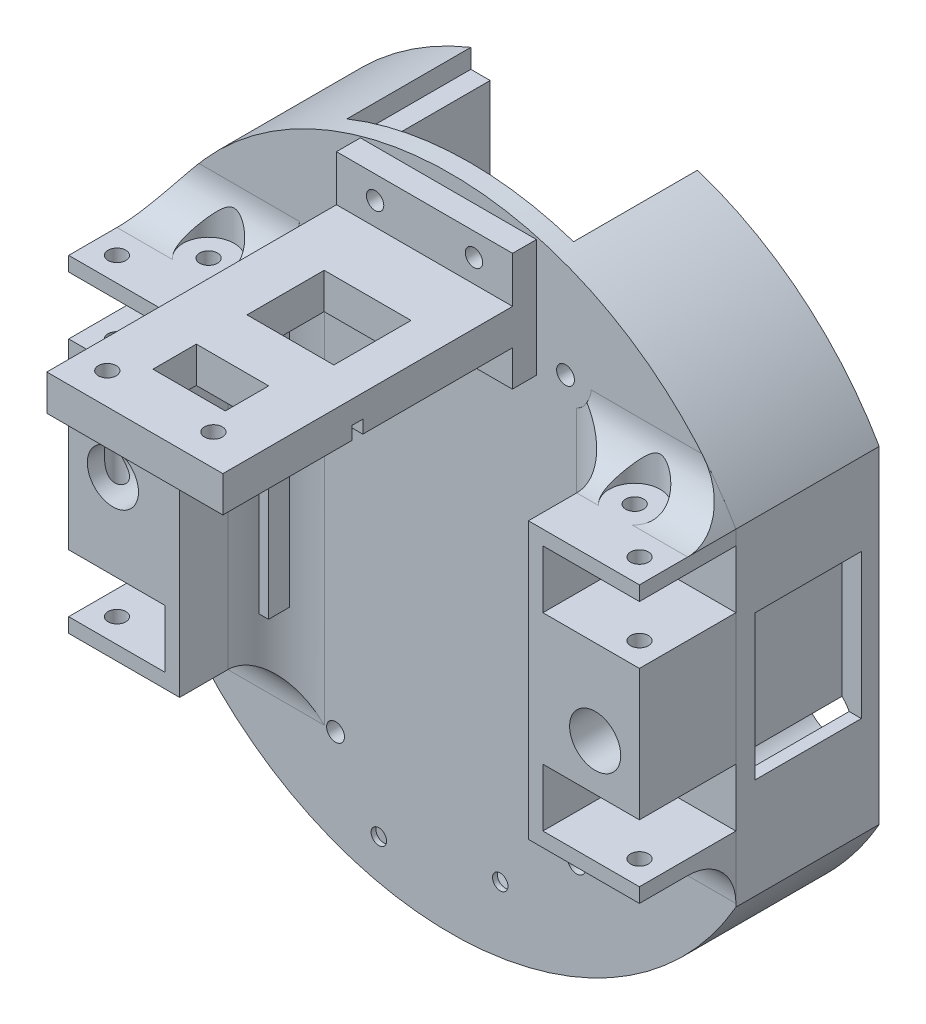
SolidWorks part; units mm, degrees
ref_plane "Alzado" through (0, 0, 0) normal (0, 0, 1) x (1, 0, 0)
ref_plane "Planta" through (0, 0, 0) normal (0, 1, 0) x (1, 0, 0)
ref_plane "Vista lateral" through (0, 0, 0) normal (1, 0, 0) x (0, 0, -1)
sketch "Croquis1" plane through (0, 0, 0) normal (0, 0, 1) x (1, 0, 0)
  line L0 (-13.4238, -120.2944) -> (-13.4238, -132.2944) construction
  line L1 (-13.4238, -132.2944) -> (-9.4238, -132.2944) construction
  line L2 (-9.4238, -132.2944) -> (-9.4238, -256.2944) construction
  line L3 (-9.4238, -256.2944) -> (33.5762, -256.2944) construction
  line L4 (33.5762, -120.2944) -> (33.5762, -256.2944) construction
  line L5 (-13.4238, -120.2944) -> (-13.4238, -132.2944)
  line L6 (-13.4238, -132.2944) -> (-9.4238, -132.2944)
  line L7 (-9.4238, -132.2944) -> (-9.4238, -256.2944)
  line L8 (-9.4238, -256.2944) -> (33.5762, -256.2944)
  line L9 (33.5762, -120.2944) -> (33.5762, -256.2944)
  circle A2 centre (12.066, -191.5898) radius 68.188
  circle A3 centre (12.066, -191.5898) radius 43.8976
extrude "Saliente-Extruir2" add sketch "Croquis1" along normal blind 25.7 contours A3 L7 L6 L5 A2 L9 L8 region at (-15.328, -130.3199, 0)
sketch "Croquis3" plane through (0, 0, 25.7) normal (0, 0, 1) x (1, 0, 0)
  circle A0 centre (12.066, -191.5898) radius 68.188
extrude "Saliente-Extruir3" add sketch "Croquis3" along normal blind 4
sketch "Croquis6" plane through (0, 0, 29.7) normal (0, 0, 1) x (1, 0, 0)
  line L0 (-47.0808, -157.6597) -> (-47.0808, -225.5199)
  line L1 (71.2129, -157.6597) -> (71.2129, -225.5199)
  circle A0 centre (12.066, -191.5898) radius 68.188 construction
  circle A1 centre (12.066, -191.5898) radius 68.188
  circle M2 centre (12.066, -191.5898) radius 68.188
extrude "Cortar-Extruir1" cut sketch "Croquis6" against normal up to surface (29.7 mm away) contours L0 M2 | L1 M2 region at (-50.7186, -191.5898, 29.7) region at (74.8507, -191.5898, 29.7)
sketch "Croquis7" plane through (-47.0808, 0, 0) normal (-1, 0, 0) x (0, 0, 1)
  line L0 (0, -157.6597) -> (29.7, -157.6597) construction
  line L1 (27.7, -164.6597) -> (2.7, -164.6597)
  line L2 (27.7, -164.6597) -> (27.7, -219.1597)
  line L3 (27.7, -219.1597) -> (2.7, -219.1597)
  line L4 (2.7, -164.6597) -> (2.7, -219.1597)
  line L5 (27.7, -164.6597) -> (2.7, -219.1597) construction
  line L6 (27.7, -219.1597) -> (2.7, -164.6597) construction
  line L7 (29.7, -157.6597) -> (29.7, -225.5199) construction
  point P0 (15.2, -191.9097)
  dimension "D1" = 54.5
  dimension "D2" = 25
  dimension "D3" = 7
  dimension "D4" = 2
extrude "Cortar-Extruir2" cut sketch "Croquis7" against normal blind 2
sketch "Croquis8" plane through (-45.0808, 0, 0) normal (-1, 0, 0) x (0, 0, 1)
  line L0 (2.7, -219.1597) -> (27.7, -219.1597) construction
  line L3 (2.7, -164.6597) -> (2.7, -219.1597) construction
  line L4 (27.7, -219.1597) -> (27.7, -164.6597) construction
  line L7 (27.7, -164.6597) -> (2.7, -164.6597) construction
  circle A0 centre (5.7, -209.1597) radius 1.6
  circle A1 centre (24.7, -174.9597) radius 1.6
  dimension "D1" = 3.2
  dimension "D2" = 3.2
  dimension "D3" = 10
  dimension "D4" = 3
  dimension "D5" = 3
  dimension "D6" = 10.3
extrude "Cortar-Extruir3" cut sketch "Croquis8" against normal blind 10
sketch "Croquis9" plane through (71.2129, 0, 0) normal (1, 0, 0) x (0, 0, -1)
  line L0 (-29.7, -157.6597) -> (-29.7, -225.5199) construction
  line L1 (-25.7, -204.6597) -> (-3.7, -204.6597)
  line L2 (-25.7, -204.6597) -> (-25.7, -174.6597)
  line L3 (-25.7, -174.6597) -> (-3.7, -174.6597)
  line L4 (-3.7, -204.6597) -> (-3.7, -174.6597)
  line L5 (-25.7, -204.6597) -> (-3.7, -174.6597) construction
  line L6 (-25.7, -174.6597) -> (-3.7, -204.6597) construction
  line L7 (0, -157.6597) -> (-29.7, -157.6597) construction
  point P0 (-14.7, -189.6597)
  dimension "D1" = 30
  dimension "D2" = 22
  dimension "D3" = 4
  dimension "D4" = 17
extrude "Cortar-Extruir4" cut sketch "Croquis9" against normal blind 4
sketch "Croquis10" plane through (0, 0, 0) normal (0, 0, -1) x (-1, 0, 0)
  circle A0 centre (11.7683, -235.5435) radius 1.85
  circle A1 centre (-38.2139, -234.2077) radius 1.85
  circle A2 centre (37.9161, -192.9255) radius 1.85
  circle A3 centre (-62.0482, -190.2541) radius 1.85
  circle A4 centre (-35.9003, -147.6361) radius 1.85
  circle A5 centre (14.0818, -148.9719) radius 1.85
extrude "Cortar-Extruir5" cut sketch "Croquis10" against normal through all
sketch "Croquis11" plane through (0, 0, 29.7) normal (0, 0, 1) x (1, 0, 0)
  line L1 (-6.6149, -135.8646) -> (29.8796, -135.8646)
  line L2 (-6.6149, -135.8646) -> (-6.6149, -150.703)
  line L3 (-6.6149, -150.703) -> (29.8796, -150.703)
  line L4 (29.8796, -135.8646) -> (29.8796, -150.703)
extrude "Saliente-Extruir4" add sketch "Croquis11" along normal up to surface (5 mm away)
sketch "Croquis12" plane through (0, 0, 34.7) normal (0, 0, 1) x (1, 0, 0)
  line L0 (-6.6149, -135.8646) -> (-6.6149, -150.703) construction
  line L1 (-6.6149, -143.2838) -> (29.8796, -143.2838)
  line L2 (-6.6149, -143.2838) -> (-6.6149, -135.8646)
  line L3 (-6.6149, -135.8646) -> (29.8796, -135.8646)
  line L4 (29.8796, -143.2838) -> (29.8796, -135.8646)
extrude "Saliente-Extruir5" add sketch "Croquis12" along normal blind 60
sketch "Croquis13" plane through (29.8796, 0, 0) normal (1, 0, 0) x (0, 0, -1)
  line L0 (-94.7, -143.2838) -> (-34.7, -143.2838) construction
  line L1 (-67.8927, -143.2838) -> (-65.6955, -143.2838)
  line L2 (-67.8927, -143.2838) -> (-67.8927, -140.5858)
  line L3 (-67.8927, -140.5858) -> (-65.6955, -140.5858)
  line L4 (-65.6955, -143.2838) -> (-65.6955, -140.5858)
extrude "Cortar-Extruir6" cut sketch "Croquis13" against normal through all
sketch "Croquis15" plane through (0, 0, 29.7) normal (0, 0, 1) x (1, 0, 0)
  line L0 (-19.658, -153.6519) -> (-19.658, -207.8491) construction
  line L1 (-19.658, -166.7959) -> (-21.658, -166.7959)
  line L2 (-19.658, -166.7959) -> (-19.658, -216.285)
  line L3 (-19.658, -216.285) -> (-21.658, -216.285)
  line L4 (-21.658, -166.7959) -> (-21.658, -216.285)
  line L5 (42.342, -153.6519) -> (42.342, -232.8491) construction
  line L6 (42.342, -166.7959) -> (44.342, -166.7959)
  line L7 (42.342, -166.7959) -> (42.342, -216.285)
  line L8 (42.342, -216.285) -> (44.342, -216.285)
  line L9 (44.342, -166.7959) -> (44.342, -216.285)
  dimension "D1" = 2
  dimension "D2" = 2
extrude "Saliente-Extruir6" add sketch "Croquis15" along normal blind 6
sketch "Croquis16" plane through (0, 0, 29.7) normal (0, 0, 1) x (1, 0, 0)
  circle A0 centre (-2.7952, -249.8624) radius 1.6
  circle A1 centre (22.3692, -245.4021) radius 1.6
  dimension "D1" = 3.2
  dimension "D2" = 3.2
extrude "Cortar-Extruir7" cut sketch "Croquis16" against normal blind 10
sketch "Croquis17" plane through (0, -143.2838, 0) normal (0, -1, 0) x (-1, 0, 0)
  circle A0 centre (0.578, -88.2) radius 1.85
  circle A1 centre (-10.0711, -88.2) radius 1.85
  circle A2 centre (-21.422, -88.2) radius 1.85
  dimension "D1" = 3.7
  dimension "D2" = 3.7
  dimension "D3" = 3.7
extrude "Cortar-Extruir8" cut sketch "Croquis17" against normal through all
sketch "Croquis23" plane through (0, 0, 29.7) normal (0, 0, 1) x (1, 0, 0)
  line L0 (-21.658, -166.7959) -> (-21.658, -216.285) construction
  line L1 (-47.0808, -157.6597) -> (-21.658, -157.6597)
  line L2 (-47.0808, -157.6597) -> (-47.0808, -175.6597)
  line L3 (-47.0808, -175.6597) -> (-21.658, -175.6597)
  line L4 (-21.658, -157.6597) -> (-21.658, -175.6597)
  line L5 (44.342, -216.285) -> (44.342, -166.7959) construction
  line L6 (-47.0808, -225.5199) -> (-21.658, -225.5199)
  line L7 (-47.0808, -225.5199) -> (-47.0808, -207.5199)
  line L8 (-47.0808, -207.5199) -> (-21.658, -207.5199)
  line L9 (-21.658, -225.5199) -> (-21.658, -207.5199)
  line L10 (71.2129, -157.6597) -> (44.342, -157.6597)
  line L11 (71.2129, -157.6597) -> (71.2129, -175.6597)
  line L12 (71.2129, -175.6597) -> (44.342, -175.6597)
  line L13 (44.342, -157.6597) -> (44.342, -175.6597)
  line L14 (71.2129, -157.6597) -> (71.2129, -225.5199) construction
  line L15 (71.2129, -214.8491) -> (44.342, -214.8491)
  line L16 (71.2129, -214.8491) -> (71.2129, -196.8491)
  line L17 (71.2129, -196.8491) -> (44.342, -196.8491)
  line L18 (44.342, -214.8491) -> (44.342, -196.8491)
  dimension "D1" = 18
  dimension "D2" = 18
  dimension "D3" = 18
  dimension "D4" = 18
extrude "Saliente-Extruir8" add sketch "Croquis23" along normal blind 20
sketch "Croquis24" plane through (0, 0, 49.7) normal (0, 0, 1) x (1, 0, 0)
  line L0 (-47.0808, -157.6597) -> (-47.0808, -175.6597) construction
  line L1 (-47.0808, -172.6597) -> (-27.0808, -172.6597)
  line L2 (-47.0808, -172.6597) -> (-47.0808, -160.6597)
  line L3 (-47.0808, -160.6597) -> (-27.0808, -160.6597)
  line L4 (-27.0808, -172.6597) -> (-27.0808, -160.6597)
  line L5 (-47.0808, -207.5199) -> (-47.0808, -225.5199) construction
  line L6 (-47.0808, -222.5199) -> (-27.0808, -222.5199)
  line L7 (-47.0808, -222.5199) -> (-47.0808, -210.5199)
  line L8 (-47.0808, -210.5199) -> (-27.0808, -210.5199)
  line L9 (-27.0808, -222.5199) -> (-27.0808, -210.5199)
  line L10 (71.2129, -175.6597) -> (71.2129, -157.6597) construction
  line L11 (71.2129, -160.6597) -> (51.2129, -160.6597)
  line L12 (71.2129, -160.6597) -> (71.2129, -172.6597)
  line L13 (71.2129, -172.6597) -> (51.2129, -172.6597)
  line L14 (51.2129, -160.6597) -> (51.2129, -172.6597)
  line L15 (71.2129, -214.8491) -> (71.2129, -196.8491) construction
  line L16 (71.2129, -199.8491) -> (51.2129, -199.8491)
  line L17 (71.2129, -199.8491) -> (71.2129, -211.8491)
  line L18 (71.2129, -211.8491) -> (51.2129, -211.8491)
  line L19 (51.2129, -199.8491) -> (51.2129, -211.8491)
  line L20 (-21.658, -157.6597) -> (-47.0808, -157.6597) construction
  line L21 (-47.0808, -225.5199) -> (-21.658, -225.5199) construction
  line L22 (71.2129, -157.6597) -> (44.342, -157.6597) construction
  line L23 (71.2129, -196.8491) -> (44.342, -196.8491) construction
  line L24 (-47.0808, -175.6597) -> (-21.658, -175.6597) construction
  line L25 (-21.658, -157.6597) -> (-24.0808, -157.6597)
  line L26 (-21.658, -157.6597) -> (-21.658, -175.6597)
  line L27 (-21.658, -175.6597) -> (-24.0808, -175.6597)
  line L28 (-24.0808, -157.6597) -> (-24.0808, -175.6597)
  line L29 (-47.0808, -225.5199) -> (-21.658, -225.5199) construction
  line L30 (-21.658, -207.5199) -> (-24.0808, -207.5199)
  line L31 (-21.658, -207.5199) -> (-21.658, -225.5199)
  line L32 (-21.658, -225.5199) -> (-24.0808, -225.5199)
  line L33 (-24.0808, -207.5199) -> (-24.0808, -225.5199)
  line L34 (44.342, -175.6597) -> (71.2129, -175.6597) construction
  line L35 (44.342, -157.6597) -> (48.2129, -157.6597)
  line L36 (44.342, -157.6597) -> (44.342, -175.6597)
  line L37 (44.342, -175.6597) -> (48.2129, -175.6597)
  line L38 (48.2129, -157.6597) -> (48.2129, -175.6597)
  line L39 (44.342, -214.8491) -> (71.2129, -214.8491) construction
  line L40 (44.342, -196.8491) -> (48.2129, -196.8491)
  line L41 (44.342, -196.8491) -> (44.342, -214.8491)
  line L42 (44.342, -214.8491) -> (48.2129, -214.8491)
  line L43 (48.2129, -196.8491) -> (48.2129, -214.8491)
  dimension "D1" = 12
  dimension "D2" = 12
  dimension "D3" = 12
  dimension "D4" = 12
  dimension "D5" = 3
  dimension "D6" = 3
  dimension "D7" = 3
  dimension "D8" = 3
  dimension "D9" = 20
  dimension "D10" = 20
  dimension "D11" = 20
  dimension "D12" = 20
  dimension "D13" = 3
  dimension "D14" = 3
  dimension "D15" = 3
  dimension "D16" = 3
extrude "Cortar-Extruir12" cut sketch "Croquis24" against normal blind 20
sketch "Croquis25" plane through (0, -157.6597, 0) normal (0, 1, 0) x (1, 0, 0)
  line L0 (-47.0808, -49.7) -> (-47.0808, -29.7) construction
  line L2 (-24.0808, -49.7) -> (-47.0808, -49.7) construction
  line L3 (-24.0808, -29.7) -> (-24.0808, -49.7) construction
  line L4 (-24.0808, -29.7) -> (-47.0808, -29.7) construction
  line L5 (12.0762, -94.7) -> (12.0762, 4.7088) construction
  line L6 (29.8796, -94.7) -> (-6.6149, -94.7) construction
  circle A0 centre (-42.0808, -44.7) radius 1.85
  circle A1 centre (-32.0808, -35.7) radius 1.85
  circle A2 centre (66.2332, -44.7) radius 1.85
  circle A3 centre (56.2332, -35.7) radius 1.85
  dimension "D1" = 3.7
  dimension "D2" = 3.7
  dimension "D3" = 5
  dimension "D4" = 5
  dimension "D5" = 8
  dimension "D6" = 6
extrude "Cortar-Extruir13" cut sketch "Croquis25" against normal through all
sketch "Croquis26" plane through (0, 0, 0) normal (0, 0, -1) x (-1, 0, 0)
  line L0 (-12.066, -191.5898) -> (-12.066, -114.417) construction
  circle A1 centre (34.6799, -216.4704) radius 7
  circle A2 centre (34.6799, -167.6419) radius 7
  circle A5 centre (-58.812, -167.6419) radius 7
  circle A6 centre (-62.4, -207.7488) radius 7
  dimension "D2" = 14
  dimension "D3" = 14
extrude "Cortar-Extruir14" cut sketch "Croquis26" against normal blind 23
sketch "Croquis27" plane through (0, 0, 25.7) normal (0, 0, -1) x (-1, 0, 0)
  line L1 (-25.7146, -247.8694) -> (-21.9051, -249.533)
  line L2 (-21.9051, -249.533) -> (-18.5596, -247.0657)
  line L3 (-18.5596, -247.0657) -> (-19.0237, -242.9347)
  line L4 (-19.0237, -242.9347) -> (-22.8332, -241.2711)
  line L5 (-22.8332, -241.2711) -> (-26.1787, -243.7385)
  line L6 (-26.1787, -243.7385) -> (-25.7146, -247.8694)
  line L7 (0.3215, -253.2032) -> (4.4516, -253.6751)
  line L8 (4.4516, -253.6751) -> (6.9252, -250.3343)
  line L9 (6.9252, -250.3343) -> (5.2688, -246.5216)
  line L10 (5.2688, -246.5216) -> (1.1388, -246.0498)
  line L11 (1.1388, -246.0498) -> (-1.3349, -249.3906)
  line L12 (-1.3349, -249.3906) -> (0.3215, -253.2032)
  circle A0 centre (-22.3692, -245.4021) radius 3.6 construction
  circle A1 centre (2.7952, -249.8624) radius 3.6 construction
  dimension "D1" = 7.2
  dimension "D2" = 7.2
extrude "Cortar-Extruir15" cut sketch "Croquis27" against normal blind 3
sketch "Croquis28" plane through (0, -135.8646, 0) normal (0, 1, 0) x (1, 0, 0)
  line L0 (29.8796, -94.7) -> (29.8796, -29.7) construction
  line L1 (3.8796, -74.2) -> (18.8796, -74.2)
  line L2 (3.8796, -74.2) -> (3.8796, -83.2)
  line L3 (3.8796, -83.2) -> (18.8796, -83.2)
  line L4 (18.8796, -74.2) -> (18.8796, -83.2)
  line L5 (3.8796, -74.2) -> (18.8796, -83.2) construction
  line L6 (3.8796, -83.2) -> (18.8796, -74.2) construction
  line L7 (29.8796, -94.7) -> (-6.6149, -94.7) construction
  line L9 (3.8796, -47.7) -> (21.8796, -47.7)
  line L10 (3.8796, -47.7) -> (3.8796, -63.7)
  line L11 (3.8796, -63.7) -> (21.8796, -63.7)
  line L12 (21.8796, -47.7) -> (21.8796, -63.7)
  line L13 (3.8796, -47.7) -> (21.8796, -63.7) construction
  line L14 (3.8796, -63.7) -> (21.8796, -47.7) construction
  point P0 (11.3796, -78.7)
  point P9 (12.8796, -55.7)
  dimension "D1" = 15
  dimension "D2" = 9
  dimension "D3" = 11
  dimension "D4" = 16
  dimension "D5" = 18
  dimension "D6" = 16
  dimension "D7" = 8
  dimension "D8" = 31
extrude "Cortar-Extruir16" cut sketch "Croquis28" against normal blind 10
sketch "Croquis29" plane through (0, -135.8646, 0) normal (0, 1, 0) x (1, 0, 0)
  circle A0 centre (10.0711, -88.2) radius 1.85
extrude "Saliente-Extruir9" add sketch "Croquis29" against normal up to surface (7.4192 mm away) up to face at (11.3796, -143.2838, 78.7)
sketch "Croquis30" plane through (0, 0, 29.7) normal (0, 0, 1) x (1, 0, 0)
  line L0 (48.2129, -175.6597) -> (71.2129, -175.6597) construction
  line L1 (-47.0808, -175.6597) -> (-24.0808, -175.6597)
  line L2 (-47.0808, -175.6597) -> (-47.0808, -207.5199)
  line L3 (-47.0808, -207.5199) -> (-24.0808, -207.5199)
  line L4 (-24.0808, -175.6597) -> (-24.0808, -207.5199)
  line L5 (48.2129, -175.6597) -> (71.2129, -175.6597)
  line L6 (48.2129, -175.6597) -> (48.2129, -196.8491)
  line L7 (48.2129, -196.8491) -> (71.2129, -196.8491)
  line L8 (71.2129, -175.6597) -> (71.2129, -196.8491)
  line L9 (71.2129, -175.6597) -> (71.2129, -196.8491) construction
  line L10 (71.2129, -196.8491) -> (48.2129, -196.8491) construction
  circle A0 centre (-37.9161, -192.9255) radius 5.3
  circle A1 centre (62.0482, -190.2541) radius 5.3
  dimension "D1" = 10.6
  dimension "D2" = 10.6
extrude "Saliente-Extruir10" add sketch "Croquis30" along normal up to surface (20 mm away) up to face at (-36.3308, -166.6597, 49.7)
sketch "Croquis31" plane through (0, -225.5199, 0) normal (0, -1, 0) x (1, 0, 0)
  circle A0 centre (-42.0808, 44.7) radius 1.85
  circle A1 centre (-32.0808, 35.7) radius 1.85
  circle A2 centre (56.2332, 35.7) radius 1.85
  circle A3 centre (66.2332, 44.7) radius 1.85
extrude "Cortar-Extruir17" cut sketch "Croquis31" against normal through all
fillet "Redondeo2" radius 10 6 edges at (59.7129, -157.6597, 29.7) (-35.5808, -157.6597, 29.7) (48.2129, -186.2544, 29.7) (-24.0808, -191.5898, 29.7) (59.7129, -214.8491, 29.7) (-35.5808, -225.5199, 29.7)
sketch "Croquis32" plane through (0, 0, 29.7) normal (0, 0, 1) x (1, 0, 0)
  circle A0 centre (-14.0818, -148.9719) radius 5.3
  circle A1 centre (35.9003, -147.6361) radius 5.3
  dimension "D1" = 10.6
  dimension "D2" = 10.6
extrude "Cortar-Extruir18" cut sketch "Croquis32" along normal through all
sketch "Croquis33" plane through (0, -225.5199, 0) normal (0, -1, 0) x (1, 0, 0)
  circle A0 centre (-32.0808, 35.7) radius 5.3
  circle A1 centre (56.2332, 35.7) radius 5.3
  dimension "D1" = 10.6
  dimension "D2" = 10.6
extrude "Cortar-Extruir19" cut sketch "Croquis33" along normal blind 10
sketch "Croquis35" plane through (0, -157.6597, 0) normal (0, 1, 0) x (1, 0, 0)
  circle A0 centre (-32.0808, -35.7) radius 5.3
  circle A1 centre (56.2332, -35.7) radius 5.3
  dimension "D1" = 10.6
  dimension "D2" = 10.6
extrude "Cortar-Extruir21" cut sketch "Croquis35" along normal blind 10
sketch "Croquis37" plane through (0, -214.8491, 0) normal (0, -1, 0) x (1, 0, 0)
  circle A0 centre (56.2332, 35.7) radius 5.3
  dimension "D1" = 10.6
extrude "Cortar-Extruir23" cut sketch "Croquis37" along normal blind 10
sketch "Croquis38" plane through (-6.6149, 0, 0) normal (-1, 0, 0) x (0, 0, 1)
  line L0 (94.7, -135.8646) -> (29.7, -135.8646) construction
  line L1 (34.6572, -135.8646) -> (29.7026, -135.8646)
  line L2 (34.6572, -135.8646) -> (34.6572, -126.3384)
  line L3 (34.6572, -126.3384) -> (29.7026, -126.3384)
  line L4 (29.7026, -135.8646) -> (29.7026, -126.3384)
  point P7 (34.6572, -125.2854)
  point P8 (29.7026, -126.3384)
extrude "Saliente-Extruir11" add sketch "Croquis38" against normal up to surface (36.4945 mm away) up to face at (29.8796, -142.7442, 58.5376)
sketch "Croquis39" plane through (0, 0, 34.6572) normal (0, 0, 1) x (1, 0, 0)
  line L0 (-6.6149, -131.1015) -> (29.8796, -131.1015) construction
  line L1 (-6.6149, -135.8646) -> (-6.6149, -126.3384) construction
  line L2 (29.8796, -126.3384) -> (29.8796, -135.8646) construction
  circle A0 centre (1.3851, -131.1015) radius 1.8
  circle A1 centre (21.8796, -131.1015) radius 1.8
  dimension "D1" = 3.6
  dimension "D2" = 3.6
  dimension "D3" = 8
  dimension "D4" = 8
extrude "Cortar-Extruir24" cut sketch "Croquis39" against normal through all
sketch "Croquis40" plane through (0, 0, 25.7) normal (0, 0, -1) x (-1, 0, 0)
  line L1 (-18.5232, -132.7802) -> (-18.7476, -129.0341)
  line L2 (-18.7476, -129.0341) -> (-22.1041, -127.3555)
  line L3 (-22.1041, -127.3555) -> (-25.236, -129.4229)
  line L4 (-25.236, -129.4229) -> (-25.0115, -133.169)
  line L5 (-25.0115, -133.169) -> (-21.6551, -134.8476)
  line L6 (-21.6551, -134.8476) -> (-18.5232, -132.7802)
  line L7 (-0.4642, -134.7396) -> (2.226, -132.123)
  line L8 (2.226, -132.123) -> (1.305, -128.485)
  line L9 (1.305, -128.485) -> (-2.3061, -127.4635)
  line L10 (-2.3061, -127.4635) -> (-4.9962, -130.0801)
  line L11 (-4.9962, -130.0801) -> (-4.0753, -133.7181)
  line L12 (-4.0753, -133.7181) -> (-0.4642, -134.7396)
  circle A0 centre (-21.8796, -131.1015) radius 3.25 construction
  circle A1 centre (-1.3851, -131.1015) radius 3.25 construction
  dimension "D1" = 6.5
  dimension "D2" = 6.5
extrude "Cortar-Extruir25" cut sketch "Croquis40" against normal blind 3
ref_plane "Plano1" through (0, 0, 29.7) normal (0, 0, 1) x (1, 0, 0)
sketch "Croquis44" plane through (-6.6149, 0, 0) normal (-1, 0, 0) x (0, 0, 1)
  line L0 (29.7, -126.3384) -> (29.7, -150.1607) construction
  line L1 (29.7, -19.6164) -> (29.7, 19.6164) construction
split "Partir1" trim tools "Plano1" bodies to split 139 resulting bodies 140 141 142 143
